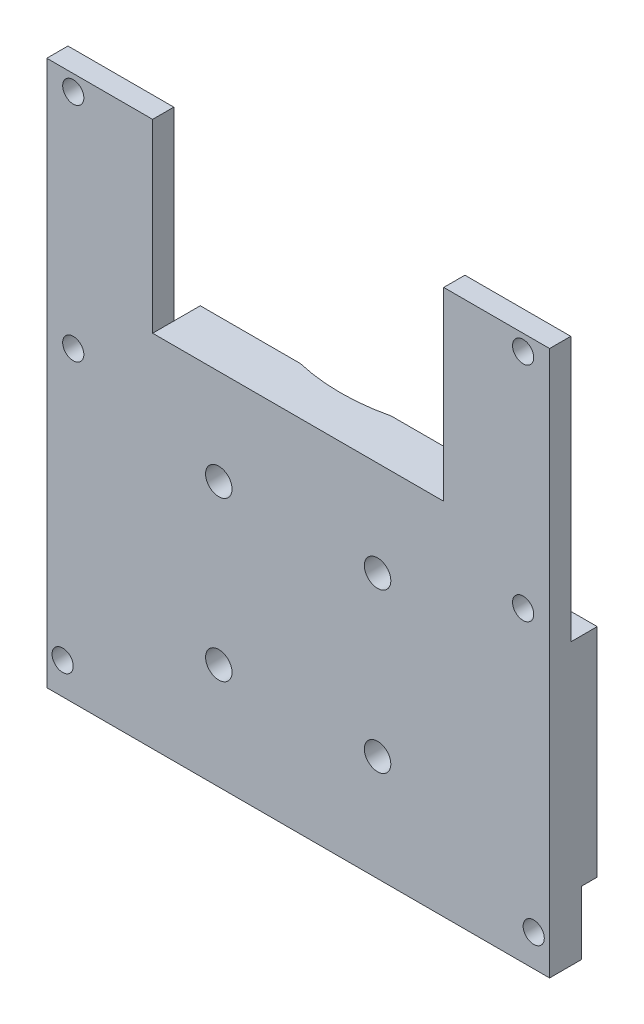
SolidWorks part; units mm, degrees
ref_plane "Front Plane" through (0, 0, 0) normal (0, 0, 1) x (1, 0, 0)
ref_plane "Top Plane" through (0, 0, 0) normal (0, 1, 0) x (1, 0, 0)
ref_plane "Right Plane" through (0, 0, 0) normal (1, 0, 0) x (0, 0, -1)
sketch "Sketch1" plane through (0, 0, 0) normal (0, 1, 0) x (1, 0, 0)
  circle A0 centre (0, 0) radius 37.5
  dimension "D1" = 75
extrude "Boss-Extrude1" add sketch "Sketch1" along normal blind 12
sketch "Sketch2" plane through (0, 12, 0) normal (0, 1, 0) x (1, 0, 0)
  circle A0 centre (0, 0) radius 30
  dimension "D1" = 60
extrude "Boss-Extrude2" add sketch "Sketch2" along normal blind 56
ref_plane "Plane1" through (0, 0, 37.5) normal (0, 0, 1) x (1, 0, 0)
sketch "Sketch4" plane through (0, 0, 37.5) normal (0, 0, 1) x (1, 0, 0)
  line L1 (37.5, 83) -> (-37.5, 83)
  line L2 (30, 68) -> (-30, 68)
  line L3 (37.5, 68) -> (-37.5, 68)
  line L4 (-37.5, 83) -> (-37.5, 68)
  line L5 (37.5, 83) -> (37.5, 68)
  line L6 (-37.5, 12) -> (-37.5, 0) construction
  line L7 (0, 68) -> (0, 76) construction
  circle A0 centre (0, 76) radius 3.5
  dimension "D4" = 7
  dimension "D2" = 75
  dimension "D5" = 8
  dimension "D1" = 0
  dimension "D3" = 15
extrude "Boss-Extrude3" add sketch "Sketch4" along normal blind 5 and the other way blind 1 separate body
other "Move Face3" face at (-37.5, 75.5, 39.5) face at (37.5, 75.5, 39.5) offset 10 parameters "D1"=10
sketch "Sketch6" plane through (0, 0, 0) normal (0, -1, 0) x (1, 0, 0)
  line L0 (0, 0) -> (0, -42.5) construction
  line L1 (-37.5, 0) -> (-42.5, 0) construction
  line L2 (37.5, 0) -> (42.5, 0) construction
  line L3 (0, 0) -> (-37.5, 0) construction
  line L4 (0, 0) -> (37.5, 0) construction
  line L5 (42.5, 0) -> (37.5, 0)
  line L6 (-37.5, 0) -> (-42.5, 0)
  circle A2 centre (0, 0) radius 42.5
  arc A3 (42.5, 0) -> (-42.5, 0) centre (0, 0) ccw
  arc A4 (0, -37.5) -> (37.5, 0) centre (0, 0) ccw construction
  circle A5 centre (0, 0) radius 37.5
  arc A6 (37.5, 0) -> (-37.5, 0) centre (0, 0) ccw
  arc A7 (0, -42.5) -> (42.5, 0) centre (0, 0) ccw construction
  arc A8 (-37.5, 0) -> (0, -37.5) centre (0, 0) ccw construction
  arc A9 (-42.5, 0) -> (0, -42.5) centre (0, 0) ccw construction
  circle A13 centre (0, 0) radius 42.5 construction
  circle A15 centre (0, 0) radius 42.5 construction
  dimension "D3" = 90
  dimension "D4" = 90
  dimension "D1" = 5
  dimension "D2" = 0
extrude "Boss-Extrude4" add sketch "Sketch6" against normal up to surface (12 mm away) separate body up to face at (0, 12, 30)
delete or keep bodies "Body-Delete/Keep 1" type delete bodies bodies 102
sketch "Sketch7" plane through (0, 68, 0) normal (0, -1, 0) x (1, 0, 0)
  line L9 (-8.6023, 36.5) -> (8.6023, 36.5) construction
  line L10 (8.6023, 36.5) -> (47.5, 36.5)
  line L17 (47.5, 36.5) -> (47.5, 42.5)
  line L18 (47.5, 42.5) -> (-47.5, 42.5)
  line L19 (-47.5, 42.5) -> (-47.5, 36.5)
  line L20 (-47.5, 36.5) -> (47.5, 36.5)
  line L21 (47.5, 36.5) -> (47.5, 42.5)
  line L22 (47.5, 42.5) -> (-47.5, 42.5)
  line L23 (-47.5, 42.5) -> (-47.5, 36.5)
  line L24 (-47.5, 36.5) -> (-8.6023, 36.5)
  arc A2 (-8.6023, 36.5) -> (-37.5, 0) centre (0, 0) ccw construction
  arc A4 (37.5, 0) -> (-37.5, 0) centre (0, 0) ccw
  arc A5 (8.6023, 36.5) -> (-8.6023, 36.5) centre (0, 0) ccw
  arc A6 (37.5, 0) -> (8.6023, 36.5) centre (0, 0) ccw construction
  dimension "D1" = 0
  dimension "D2" = 0
extrude "Boss-Extrude5" add sketch "Sketch7" along normal up to surface (68 mm away) up to face at (0, 0, 20)
other "Move Face1" face at (0, 41.5, 42.5) offset 10 parameters "D1"=10
sketch "Sketch11" plane through (0, 0, 0) normal (0, -1, 0) x (1, 0, 0)
  line L1 (-47.5, 37.5) -> (47.5, 37.5)
  line L2 (-21.7715, 36.5) -> (-8.6023, 36.5)
  line L3 (-21.7715, 36.5) -> (-8.6023, 36.5) construction
  line L4 (-21.7715, 37.5) -> (-8.6023, 37.5) construction
  line L5 (47.5, 36.5) -> (47.5, 52.5) construction
  line L6 (47.5, 37.5) -> (47.5, 52.5)
  line L7 (47.5, 52.5) -> (-47.5, 52.5)
  line L8 (-47.5, 52.5) -> (-47.5, 37.5)
  dimension "D1" = 0
  dimension "D2" = 1
extrude "Boss-Extrude7" add sketch "Sketch11" along normal blind 20
sketch "Sketch12" plane through (0, 0, 37.5) normal (0, 0, -1) x (-1, 0, 0)
  line L0 (0, 0) -> (0, 35)
  line L3 (15, 20) -> (-15, 20) construction
  line L4 (15, 20) -> (15, 50) construction
  line L5 (15, 50) -> (-15, 50) construction
  line L6 (-15, 20) -> (-15, 50) construction
  line L7 (15, 20) -> (-15, 50) construction
  line L8 (15, 50) -> (-15, 20) construction
  circle A0 centre (0, 35) radius 25 construction
  circle A2 centre (-15, 50) radius 2.5
  circle A3 centre (15, 50) radius 2.5
  circle A4 centre (15, 20) radius 2.5
  circle A5 centre (-15, 20) radius 2.5
  dimension "D1" = 50
  dimension "D4" = 30
  dimension "D5" = 5
  dimension "D2" = 35
  dimension "D3" = 30
extrude "Cut-Extrude1" cut sketch "Sketch12" against normal through all both and the other way through all contours A5 | A4 | A2 | A3 region at (-15, 20, 37.5) region at (15, 20, 37.5)
sketch "Sketch13" plane through (0, 0, 36.5) normal (0, 0, -1) x (-1, 0, 0)
  circle A2 centre (-15, 50) radius 6.5
  circle A3 centre (-15, 50) radius 6.5
  circle A5 centre (15, 50) radius 6.5
  circle A6 centre (15, 50) radius 6.5
  circle A9 centre (-15, 20) radius 6.5
  circle A12 centre (15, 20) radius 6.5
  dimension "D1" = 4
  dimension "D2" = 4
extrude "Cut-Extrude2" cut sketch "Sketch13" against normal blind 5
other "Move Face2" flip direction yes face at (-17.5, 20, 52.5) offset 7 parameters "D1"=7
other "DeleteFace1" face at (0, -8, 37.5) face at (0, -20, 41.5) and patch yes
sketch "Sketch14" plane through (0, 0, 36.5) normal (0, 0, -1) x (-1, 0, 0)
  line L2 (47.5, 0) -> (-42.5, 0)
  line L16 (-42.5, 12) -> (47.5, 12)
  line L17 (47.5, 83) -> (47.5, 0) construction
  line L18 (47.5, 12) -> (47.5, 0)
  line L19 (-42.5, 0) -> (-47.5, 0)
  line L20 (-47.5, 0) -> (-47.5, 12)
  line L21 (-47.5, 0) -> (-47.5, 83) construction
  line L22 (-47.5, 12) -> (-42.5, 12)
extrude "Cut-Extrude3" cut sketch "Sketch14" against normal blind 3 and the other way through all
sketch "Sketch15" plane through (0, 0, 39.5) normal (0, 0, -1) x (-1, 0, 0)
  line L0 (0, 0) -> (0, 12) construction
  line L1 (47.5, 0) -> (47.5, 12) construction
  line L2 (-44.5, 6) -> (44.5, 6) construction
  line L3 (47.5, 12) -> (-47.5, 12) construction
  circle A0 centre (44.5, 6) radius 2
  circle A1 centre (-44.5, 6) radius 2
  point P8 (0, 6)
  dimension "D2" = 4
  dimension "D1" = 3
extrude "Cut-Extrude4" cut sketch "Sketch15" against normal through all
other "Move Face4" face at (0, 83, 41) offset 20 parameters "D1"=20
sketch "Sketch16" plane through (0, 0, 36.5) normal (0, 0, -1) x (-1, 0, 0)
  line L0 (-27.5, 103) -> (-27.5, 68)
  line L1 (-47.5, 103) -> (47.5, 103) construction
  line L2 (-27.5, 68) -> (27.5, 68)
  line L3 (27.5, 68) -> (27.5, 103)
  line L4 (47.5, 103) -> (47.5, 12) construction
  line L5 (-47.5, 12) -> (-47.5, 103) construction
  line L6 (-27.5, 103) -> (27.5, 103)
  dimension "D1" = 20
  dimension "D2" = 20
  dimension "D3" = 35
extrude "Cut-Extrude5" cut sketch "Sketch16" against normal blind 10
sketch "Sketch17" plane through (0, 0, 36.5) normal (0, 0, -1) x (-1, 0, 0)
  line L0 (27.5, 103) -> (47.5, 103)
  line L1 (47.5, 103) -> (47.5, 53)
  line L2 (47.5, 103) -> (47.5, 12) construction
  line L3 (47.5, 53) -> (27.5, 53)
  line L4 (27.5, 53) -> (27.5, 103)
  line L5 (0, 5.1793) -> (0, -5.1793) construction
  line L6 (-47.5, 53) -> (-27.5, 53)
  line L7 (-47.5, 103) -> (-47.5, 53)
  line L8 (-27.5, 103) -> (-47.5, 103)
  line L9 (-27.5, 53) -> (-27.5, 103)
  dimension "D1" = 50
extrude "Cut-Extrude6" cut sketch "Sketch17" against normal blind 5
sketch "Sketch18" plane through (0, 0, 41.5) normal (0, 0, -1) x (-1, 0, 0)
  line L0 (-47.5, 53) -> (-27.5, 53) construction
  line L1 (-47.5, 103) -> (-47.5, 53) construction
  line L2 (-27.5, 103) -> (-47.5, 103) construction
  line L3 (0, 5.1793) -> (0, -5.1793) construction
  circle A0 centre (-42.5, 58) radius 2
  circle A1 centre (-42.5, 100) radius 2
  circle A2 centre (42.5, 100) radius 2
  circle A3 centre (42.5, 58) radius 2
  dimension "D2" = 5
  dimension "D3" = 4
  dimension "D4" = 4
  dimension "D5" = 5
  dimension "D6" = 3
  dimension "D1" = 5
extrude "Cut-Extrude7" cut sketch "Sketch18" against normal through all
